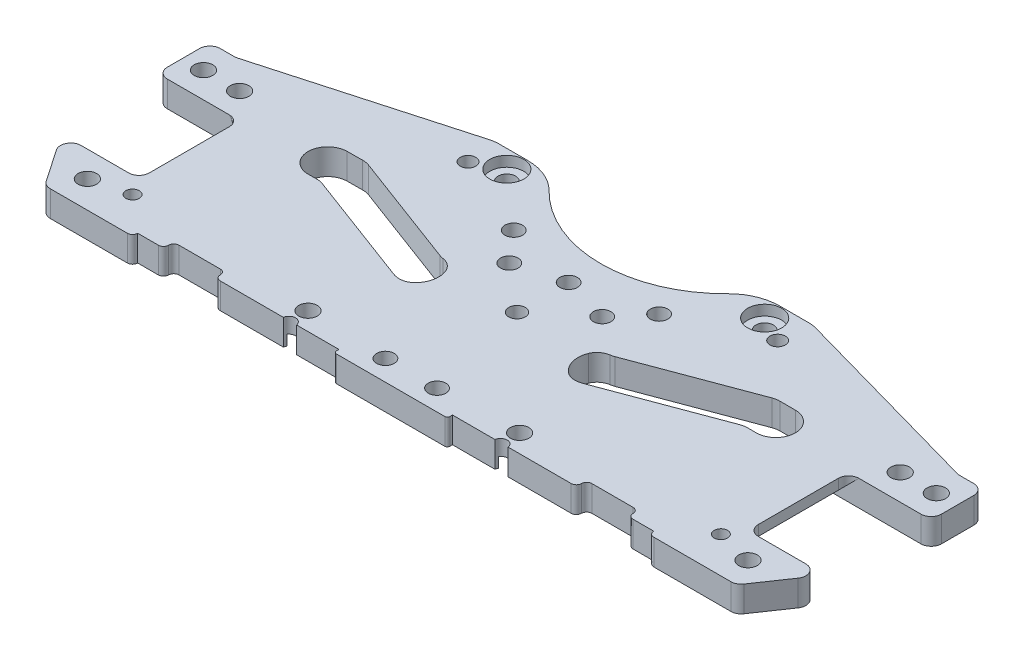
SolidWorks part; units mm, degrees
ref_plane "Front Plane" through (0, 0, 0) normal (0, 0, 1) x (1, 0, 0)
ref_plane "Top Plane" through (0, 0, 0) normal (0, 1, 0) x (1, 0, 0)
ref_plane "Right Plane" through (0, 0, 0) normal (1, 0, 0) x (0, 0, -1)
sketch "Sketch2" plane through (0, 0, 0) normal (0, 1, 0) x (1, 0, 0)
  line L0 (0, 25.4) -> (0, -25.4) construction
  line L1 (95.25, 25.4) -> (-95.25, 25.4)
  line L2 (-95.25, 25.4) -> (-95.25, 12.3825)
  line L3 (-95.25, 12.3825) -> (-74.93, 12.3825)
  line L4 (-74.93, 12.3825) -> (-74.93, -12.3825)
  line L5 (-74.93, -12.3825) -> (-95.25, -12.3825)
  line L6 (-95.25, -12.3825) -> (-95.25, -25.4)
  line L7 (-95.25, -25.4) -> (95.25, -25.4)
  line L8 (-74.93, 0) -> (74.93, 0) construction
  line L9 (95.25, -12.3825) -> (95.25, -25.4)
  line L10 (74.93, -12.3825) -> (95.25, -12.3825)
  line L11 (74.93, 12.3825) -> (74.93, -12.3825)
  line L12 (95.25, 12.3825) -> (74.93, 12.3825)
  line L13 (95.25, 25.4) -> (95.25, 12.3825)
  circle A0 centre (-90.17, 18.7325) radius 2.286
  circle A1 centre (-81.28, 18.7325) radius 2.286
  circle A3 centre (-81.28, -18.7325) radius 2.286
  circle A4 centre (81.28, -18.7325) radius 2.286
  circle A6 centre (81.28, 18.7325) radius 2.286
  circle A7 centre (90.17, 18.7325) radius 2.286
  point P3 (-74.93, 0)
  point P22 (0, 0)
  point P36 (74.93, 0)
  dimension "D7" = 4.572
  dimension "D1" = 50.8
  dimension "D2" = 24.765
  dimension "D3" = 20.32
  dimension "D4" = 74.93
  dimension "D5" = 5.08
  dimension "D6" = 8.89
  dimension "D8" = 6.35
extrude "Boss-Extrude1" add sketch "Sketch2" along normal blind 6.35
sketch "Sketch3" plane through (0, 6.35, 0) normal (0, 1, 0) x (1, 0, 0)
  line L0 (0, 3.175) -> (-20.4417, 3.175) construction
  line L7 (21.59, -1.651) -> (-21.59, -1.651)
  line L8 (19.8446, 8.001) -> (-19.8446, 8.001)
  line L9 (-22.6655, 3.5771) -> (-50.227, 13.8819) construction
  line L10 (-23.2801, -1.3454) -> (-51.3438, 9.1472)
  line L11 (-21.5347, 8.3066) -> (-49.6392, 18.8145)
  line L12 (-52.5062, 14.2838) -> (-55.1392, 14.2608) construction
  line L13 (-53.0761, 9.4527) -> (-55.0971, 9.435)
  line L14 (-51.3715, 19.1199) -> (-55.1813, 19.0867)
  line L15 (0, 8.001) -> (0, -1.651) construction
  line L16 (-55.1813, 19.0867) -> (-55.0971, 9.435) construction
  line L17 (51.3715, 19.1199) -> (55.1813, 19.0867)
  line L18 (53.0761, 9.4527) -> (55.0971, 9.435)
  line L19 (21.5347, 8.3066) -> (49.6392, 18.8145)
  line L20 (23.2801, -1.3454) -> (51.3438, 9.1472)
  arc A0 (-23.2801, -1.3454) -> (-21.59, -1.651) centre (-21.59, 3.175) ccw
  arc A2 (-49.6392, 18.8145) -> (-51.3715, 19.1199) centre (-51.3293, 14.2941) ccw
  arc A4 (-55.1813, 19.0867) -> (-55.0971, 9.435) centre (-55.1392, 14.2608) ccw
  arc A5 (-51.3438, 9.1472) -> (-53.0761, 9.4527) centre (-53.0339, 4.6268) ccw
  arc A6 (-19.8446, 8.001) -> (-21.5347, 8.3066) centre (-19.8446, 12.827) cw
  arc A7 (49.6392, 18.8145) -> (51.3715, 19.1199) centre (51.3293, 14.2941) cw
  arc A8 (55.1813, 19.0867) -> (55.0971, 9.435) centre (55.1392, 14.2608) cw
  arc A9 (51.3438, 9.1472) -> (53.0761, 9.4527) centre (53.0339, 4.6268) cw
  arc A10 (19.8446, 8.001) -> (21.5347, 8.3066) centre (19.8446, 12.827) ccw
  arc A11 (23.2801, -1.3454) -> (21.59, -1.651) centre (21.59, 3.175) cw
  arc A21 (-50.227, 13.8819) -> (-52.5062, 14.2838) centre (-52.4508, 7.9341) ccw construction
  arc A22 (-22.6655, 3.5771) -> (-20.4417, 3.175) centre (-20.4417, 9.525) ccw construction
  point P0 (0, 3.175)
  point P72 (0, -1.651)
  dimension "D15" = 6.35
  dimension "D16" = 6.35
  dimension "D2" = 21.59
  dimension "D3" = 159.5
  dimension "D4" = 159
  dimension "D5" = 31.75
  dimension "D6" = 3.81
  dimension "D7" = 9.652
  dimension "D8" = 3.175
extrude "Cut-Extrude1" cut sketch "Sketch3" against normal through all
sketch "Sketch4" plane through (0, 6.35, 0) normal (0, 1, 0) x (1, 0, 0)
  line L0 (-40.16, 39.0863) -> (-88.9, 25.4)
  line L1 (95.25, 25.4) -> (-95.25, 25.4) construction
  line L3 (-88.9, 25.4) -> (0, 25.4)
  line L4 (0, 0) -> (0, 25.4) construction
  line L5 (88.9, 25.4) -> (0, 25.4)
  line L7 (40.16, 39.0863) -> (88.9, 25.4)
  line L8 (-38.1, 39.37) -> (38.1, 39.37)
  circle A0 centre (-38.1, 31.75) radius 1.905
  arc A1 (-38.1, 39.37) -> (-40.16, 39.0863) centre (-38.1, 31.75) ccw
  arc A3 (38.1, 39.37) -> (40.16, 39.0863) centre (38.1, 31.75) cw
  circle A4 centre (38.1, 31.75) radius 1.905
  dimension "D2" = 7.62
  dimension "D3" = 3.81
  dimension "D6" = 38.1
  dimension "D1" = 6.35
  dimension "D4" = 50.8
extrude "Boss-Extrude2" add sketch "Sketch4" against normal up to surface (6.35 mm away) up to face at (0, 0, -9.8333)
sketch "Sketch5" plane through (0, 6.35, 0) normal (0, 1, 0) x (1, 0, 0)
  circle A0 centre (0, 57.15) radius 30.7975
  dimension "D2" = 61.595
  dimension "D1" = 57.15
extrude "Cut-Extrude2" cut sketch "Sketch5" against normal through all
fillet "Fillet1" radius 12.7 2 edges at (25.1467, 3.175, -39.37) (-25.1467, 3.175, -39.37)
sketch "Sketch9" plane through (0, 6.35, 0) normal (0, 1, 0) x (1, 0, 0)
  circle A0 centre (0, 57.15) radius 34.29
  dimension "D1" = 68.58
extrude "Cut-Extrude5" [suppressed] cut sketch "Sketch9" against normal through all
fillet "Fillet2" [suppressed] radius 12.7
sketch "Sketch10" plane through (0, 0, 0) normal (0, -1, 0) x (-1, 0, 0)
  circle A0 centre (-31.7299, 34.9325) radius 2.159
  circle A1 centre (-17.8858, 22.7916) radius 2.159
  circle A2 centre (0, 18.415) radius 2.159
  circle A3 centre (17.8858, 22.7916) radius 2.159
  circle A4 centre (31.7299, 34.9325) radius 2.159
  dimension "D1" = 4.318
extrude "Cut-Extrude6" cut sketch "Sketch10" against normal through all
sketch "Sketch11" plane through (0, 6.35, 0) normal (0, 1, 0) x (1, 0, 0)
  circle A0 centre (-31.7299, 34.9325) radius 4.191
  circle A1 centre (31.7299, 34.9325) radius 4.191
  dimension "D1" = 8.382
extrude "Cut-Extrude7" cut sketch "Sketch11" against normal blind 2.54
sketch "Sketch8" plane through (0, 6.35, 0) normal (0, 1, 0) x (1, 0, 0)
  line L0 (38.1, -25.4) -> (13.97, -25.4)
  line L1 (38.1, -25.4) -> (38.1, -24.13)
  line L2 (38.1, -24.13) -> (27.6663, -24.13)
  line L3 (13.97, -25.4) -> (13.97, -24.13)
  line L4 (-95.25, -25.4) -> (95.25, -25.4) construction
  line L6 (24.4037, -24.13) -> (13.97, -24.13)
  arc A1 (27.6663, -24.13) -> (24.4037, -24.13) centre (26.035, -24.384) ccw
  point P6 (26.035, -24.13)
  point P13 (26.035, -25.4)
  dimension "D3" = 1.651
  dimension "D1" = 24.13
  dimension "D2" = 1.27
  dimension "D4" = 0.254
  dimension "D5" = 26.035
extrude "Cut-Extrude4" cut sketch "Sketch8" against normal through all contours L2 L3 L0 L1 | L2 | L2 region at (26.035, 6.35, 24.6416)
sketch "Sketch6" plane through (0, 6.35, 0) normal (0, 1, 0) x (1, 0, 0)
  line L0 (38.1, -25.4) -> (95.25, -25.4) construction
  line L1 (44.45, -25.4) -> (57.15, -25.4)
  line L2 (44.45, -25.4) -> (44.45, -21.59)
  line L3 (44.45, -21.59) -> (57.15, -21.59)
  line L4 (57.15, -25.4) -> (57.15, -21.59)
  line L6 (50.8, -21.59) -> (50.8, -25.4) construction
  line L7 (44.45, -25.4) -> (38.1, -25.4)
  line L9 (44.45, -25.4) -> (44.45, -24.13)
  line L10 (44.45, -24.13) -> (38.1, -24.13)
  line L11 (38.1, -25.4) -> (38.1, -24.13)
  line L12 (63.5, -25.4) -> (63.5, -24.13)
  line L13 (57.15, -24.13) -> (63.5, -24.13)
  line L14 (57.15, -25.4) -> (57.15, -24.13)
  line L15 (57.15, -25.4) -> (63.5, -25.4)
  point P6 (50.8, -25.4)
  dimension "D1" = 50.8
  dimension "D2" = 12.7
  dimension "D3" = 3.81
extrude "Cut-Extrude3" cut sketch "Sketch6" against normal blind 7.62 contours L11 L7 L2 L10 | L4 L15 L12 L13 | L3 L6 L1 L4 | L6 L3 L2 L1 region at (47.625, 6.35, 23.495) region at (41.275, 6.35, 24.765) region at (53.975, 6.35, 23.495) region at (60.325, 6.35, 24.765)
sketch "Sketch12" plane through (0, 6.35, 0) normal (0, 1, 0) x (1, 0, 0)
  circle A0 centre (72.39, -16.51) radius 1.651
  dimension "D3" = 3.302
  dimension "D1" = 72.39
  dimension "D2" = 16.51
extrude "Cut-Extrude8" cut sketch "Sketch12" against normal through all
sketch "Sketch13" plane through (0, 0, 0) normal (0, -1, 0) x (1, 0, 0)
  line L0 (24.4037, 24.13) -> (13.97, 24.13) construction
  circle A1 centre (26.035, 19.685) radius 2.286
  arc A3 (24.4037, 24.13) -> (27.6663, 24.13) centre (26.035, 24.384) ccw construction
  point P7 (26.035, 22.733)
  dimension "D1" = 4.445
  dimension "D2" = 4.572
extrude "Cut-Extrude9" cut sketch "Sketch13" against normal through all both and the other way through all
sketch "Sketch14" plane through (0, 0, 0) normal (0, -1, 0) x (1, 0, 0)
  circle A0 centre (26.035, 19.685) radius 4.064
  dimension "D1" = 8.128
extrude "Cut-Extrude10" cut sketch "Sketch14" against normal blind 2.54
sketch "Sketch15" [suppressed] plane through (0, 6.35, 0) normal (0, 1, 0) x (1, 0, 0)
  line L0 (26.035, -22.733) -> (26.035, -19.685) construction
  line L2 (-95.25, -25.4) -> (13.97, -25.4) construction
  circle A0 centre (19.685, -19.685) radius 2.286
  arc A1 (27.6663, -24.13) -> (24.4037, -24.13) centre (26.035, -24.384) ccw construction
  circle A2 centre (32.385, -19.685) radius 2.286
  dimension "D2" = 4.572
  dimension "D1" = 5.715
  dimension "D3" = 6.35
extrude "Cut-Extrude11" [suppressed] cut sketch "Sketch15" against normal through all
sketch "Sketch16" [suppressed] plane through (0, 6.35, 0) normal (0, 1, 0) x (1, 0, 0)
  circle A0 centre (19.685, -19.685) radius 4.191
  circle A1 centre (32.385, -19.685) radius 4.191
  dimension "D1" = 8.382
extrude "Cut-Extrude12" [suppressed] cut sketch "Sketch16" against normal blind 2.54
mirror "Mirror1" about plane through (0, 0, 0) normal (1, 0, 0) of "Cut-Extrude10", "Cut-Extrude9", "Cut-Extrude8", "Cut-Extrude4", "Cut-Extrude3"
mirror "Mirror2" [suppressed] about plane through (0, 0, 0) normal (1, 0, 0)
sketch "Sketch17" plane through (0, 0, 0) normal (0, -1, 0) x (1, 0, 0)
  circle A0 centre (11.43, -15.24) radius 2.159
  circle A1 centre (-11.43, -15.24) radius 2.159
  dimension "D1" = 4.318
extrude "Cut-Extrude13" cut sketch "Sketch17" against normal through all
sketch "Sketch18" plane through (0, 0, 0) normal (0, -1, 0) x (1, 0, 0)
  circle A0 centre (-11.43, -15.24) radius 4.445
  circle A1 centre (11.43, -15.24) radius 4.445
  circle A2 centre (-38.1, -31.75) radius 4.445
  circle A3 centre (38.1, -31.75) radius 4.445
  dimension "D1" = 8.89
sketch "Sketch19" [suppressed] plane through (0, 6.35, 0) normal (0, 1, 0) x (1, 0, 0)
  circle A0 centre (-17.8858, 22.7916) radius 4.064
  circle A1 centre (0, 18.415) radius 4.064
  circle A2 centre (17.8858, 22.7916) radius 4.064
  dimension "D1" = 8.128
extrude "Cut-Extrude15" [suppressed] cut sketch "Sketch19" against normal blind 2.54
extrude "Cut-Extrude14" cut sketch "Sketch18" against normal blind 2.54
chamfer "Chamfer2" distance 3.81 angle 45 2 edges at (74.93, 0, 0) (-74.93, 0, 0)
chamfer "Chamfer3" [suppressed] distance 3.81 angle 45
fillet "Fillet3" radius 2.54 14 edges at (-88.9, 3.175, -25.4) (88.9, 3.175, -25.4) (95.25, 3.175, -25.4) (95.25, 3.175, -12.3825) (95.25, 3.175, 12.3825) (95.25, 3.175, 25.4) (-95.25, 3.175, 25.4) (-95.25, 3.175, 12.3825) (-95.25, 3.175, -25.4) (-95.25, 3.175, -12.3825) (-74.93, 5.08, -12.3825) (-74.93, 5.08, 12.3825) (74.93, 5.08, -12.3825) (74.93, 5.08, 12.3825)
fillet "Fillet4" radius 1.27 10 edges at (-57.15, 3.175, 21.59) (-44.45, 3.175, 21.59) (57.15, 3.175, 21.59) (44.45, 3.175, 21.59) (-44.45, 3.175, 24.13) (-63.5, 3.175, 25.4) (-57.15, 3.175, 24.13) (63.5, 3.175, 25.4) (57.15, 3.175, 24.13) (44.45, 3.175, 24.13)
sketch "Sketch20" plane through (0, 0, 0) normal (0, -1, 0) x (1, 0, 0)
  line L0 (0, 0) -> (0, 25.4) construction
  line L1 (-13.97, 25.4) -> (13.97, 25.4) construction
  circle A1 centre (-81.28, 18.7325) radius 4.191
  circle A3 centre (-81.28, -18.7325) radius 4.191
  circle A4 centre (-90.17, -18.7325) radius 4.191
  circle A5 centre (90.17, -18.7325) radius 4.191
  circle A6 centre (81.28, -18.7325) radius 4.191
  circle A8 centre (81.28, 18.7325) radius 4.191
  dimension "D1" = 8.382
extrude "Cut-Extrude16" cut sketch "Sketch20" against normal blind 2.54
sketch "Sketch21" plane through (0, 6.35, 0) normal (0, 1, 0) x (1, 0, 0)
  line L0 (0, 0) -> (0, -25.4) construction
  line L1 (-13.97, -25.4) -> (13.97, -25.4) construction
  circle A0 centre (-6.35, -20.32) radius 2.159
  circle A1 centre (6.35, -20.32) radius 2.159
  dimension "D3" = 4.318
  dimension "D1" = 5.08
  dimension "D2" = 6.35
extrude "Cut-Extrude17" cut sketch "Sketch21" against normal through all
sketch "Sketch22" plane through (0, 0, 0) normal (0, -1, 0) x (-1, 0, 0)
  circle A0 centre (6.35, -20.32) radius 4.445
  circle A1 centre (-6.35, -20.32) radius 4.445
  dimension "D1" = 8.89
extrude "Cut-Extrude18" cut sketch "Sketch22" against normal blind 2.54
fillet "Fillet5" radius 0.635 2 edges at (-13.97, 3.175, 25.4) (13.97, 3.175, 25.4)
fillet "Fillet6" [suppressed] radius 0.635
sketch "Sketch23" [suppressed] plane through (0, 0, 0) normal (0, -1, 0) x (1, 0, 0)
  line L0 (63.754, 15.621) -> (63.754, 14.351) construction
  line L1 (69.85, 15.621) -> (69.85, 14.351)
  line L2 (57.658, 15.621) -> (57.658, 14.351)
  line L3 (0, 0) -> (0, 25.4) construction
  line L4 (-13.335, 25.4) -> (13.335, 25.4) construction
  line L5 (-63.754, 15.621) -> (-63.754, 14.351) construction
  line L6 (-69.85, 15.621) -> (-69.85, 14.351)
  line L7 (-57.658, 15.621) -> (-57.658, 14.351)
  arc A1 (69.85, 15.621) -> (57.658, 15.621) centre (63.754, 15.621) ccw
  arc A2 (57.658, 14.351) -> (69.85, 14.351) centre (63.754, 14.351) ccw
  arc A3 (-69.85, 15.621) -> (-57.658, 15.621) centre (-63.754, 15.621) cw
  arc A4 (-57.658, 14.351) -> (-69.85, 14.351) centre (-63.754, 14.351) cw
  point P2 (63.754, 14.986)
  point P14 (-63.754, 14.986)
  dimension "D1" = 1.27
  dimension "D4" = 6.096
  dimension "D2" = 63.754
  dimension "D3" = 15.621
extrude "Cut-Extrude19" [suppressed] cut sketch "Sketch23" against normal blind 16.51
ref_plane "Plane1" [suppressed] through (1.3405, -14.1577, 5.3296) normal (-0.9948, 0, 0.1018) x (0.1018, 0, 0.9948)
sketch "Sketch25" plane through (0, 6.35, 0) normal (0, 1, 0) x (1, 0, 0)
  line L0 (0, -1.651) -> (0, 8.001) construction
  line L1 (-21.59, -1.651) -> (21.59, -1.651) construction
  line L2 (19.8446, 8.001) -> (-19.8446, 8.001) construction
  line L3 (22.86, -2.159) -> (-22.86, -2.159)
  line L4 (22.86, 9.271) -> (-22.86, 9.271)
  arc A0 (22.86, 9.271) -> (22.86, -2.159) centre (22.86, 3.556) ccw
  arc A2 (-22.86, 9.271) -> (-22.86, -2.159) centre (-22.86, 3.556) cw
  point P9 (0, -2.159)
  point P13 (0, 3.175)
  point P19 (0, 9.271)
  dimension "D1" = 11.43
  dimension "D3" = 22.86
  dimension "D2" = 0.381
extrude "Boss-Extrude3" add sketch "Sketch25" against normal blind 6.35
fillet "Fillet7" radius 3.81 4 edges at (-19.2679, 3.175, -8.001) (-20.5045, 3.175, 1.651) (20.5045, 3.175, 1.651) (19.2679, 3.175, -8.001)
sketch "Sketch26" plane through (0, 6.35, 0) normal (0, 1, 0) x (1, 0, 0)
  circle A0 centre (0, 5.715) radius 2.032
  dimension "D1" = 4.064
extrude "Cut-Extrude20" cut sketch "Sketch26" against normal through all
sketch "Sketch27" plane through (0, 0, 0) normal (0, -1, 0) x (1, 0, 0)
  circle A0 centre (0, -5.715) radius 4.445
  dimension "D1" = 8.89
extrude "Cut-Extrude21" cut sketch "Sketch27" against normal blind 2.54
chamfer "Chamfer1" distance 2.54 angle 45 2 edges at (-72.39, 0, 18.161) (72.39, 0, 18.161)
sketch "Sketch30" plane through (0, 6.35, 0) normal (0, 1, 0) x (1, 0, 0)
  line L0 (93.98, -12.3825) -> (85.09, -25.4)
  line L1 (92.71, -12.3825) -> (77.47, -12.3825) construction
  line L2 (64.77, -25.4) -> (92.71, -25.4) construction
  line L3 (85.09, -25.4) -> (95.25, -25.4)
  line L4 (95.25, -25.4) -> (95.25, -12.3825)
  line L5 (95.25, -12.3825) -> (93.98, -12.3825)
  line L6 (0, 0) -> (0, -25.4) construction
  line L7 (-13.335, -25.4) -> (13.335, -25.4) construction
  line L8 (95.25, -22.86) -> (95.25, -14.9225) construction
  line L9 (-95.25, -12.3825) -> (-93.98, -12.3825)
  line L10 (-95.25, -25.4) -> (-95.25, -12.3825)
  line L11 (-85.09, -25.4) -> (-95.25, -25.4)
  line L12 (-93.98, -12.3825) -> (-85.09, -25.4)
  dimension "D1" = 10.16
  dimension "D2" = 1.27
extrude "Cut-Extrude24" cut sketch "Sketch30" against normal through all
fillet "Fillet8" radius 2.54 4 edges at (93.8092, 3.175, 12.6326) (85.09, 3.175, 25.4) (-93.8092, 3.175, 12.6326) (-85.09, 3.175, 25.4)
sketch "Sketch31" [suppressed] plane through (0, 6.35, 0) normal (0, 1, 0) x (1, 0, 0)
  line L0 (0, 0) -> (0, -25.4) construction
  line L1 (-13.335, -25.4) -> (13.335, -25.4) construction
  circle A0 centre (-90.17, -18.7325) radius 2.286
  circle A1 centre (90.17, -18.7325) radius 2.286
  point P9 (-81.28, -18.7325)
  point P10 (-90.17, 18.7325)
  dimension "D1" = 4.572
extrude "Cut-Extrude25" [suppressed] cut sketch "Sketch31" against normal through all
sketch "Sketch32" [suppressed] plane through (0, 6.35, 0) normal (0, 1, 0) x (1, 0, 0)
  line L0 (11.4902, 7.2628) -> (17.0942, -7.7258)
  line L1 (11.4902, 7.2628) -> (59.0731, 25.0534)
  line L2 (17.0942, -7.7258) -> (64.6771, 10.0647)
  line L3 (59.0731, 25.0534) -> (64.6771, 10.0647)
  line L4 (49.6392, 18.8145) -> (21.5347, 8.3066) construction
  line L5 (23.2801, -1.3454) -> (51.3438, 9.1472) construction
  line L7 (-133.7238, 82.8825) -> (125.0072, 82.8825)
  line L8 (-133.7238, 82.8825) -> (-133.7238, -55.4687)
  line L9 (-133.7238, -55.4687) -> (125.0072, -55.4687)
  line L10 (125.0072, 82.8825) -> (125.0072, -55.4687)
  dimension "D1" = 2.54
  dimension "D2" = 50.8
  dimension "D3" = 3.81
extrude "Cut-Extrude26" [suppressed] cut sketch "Sketch32" against normal through all contours L10 L7 L8 L9 L1 L3 L2 L0
